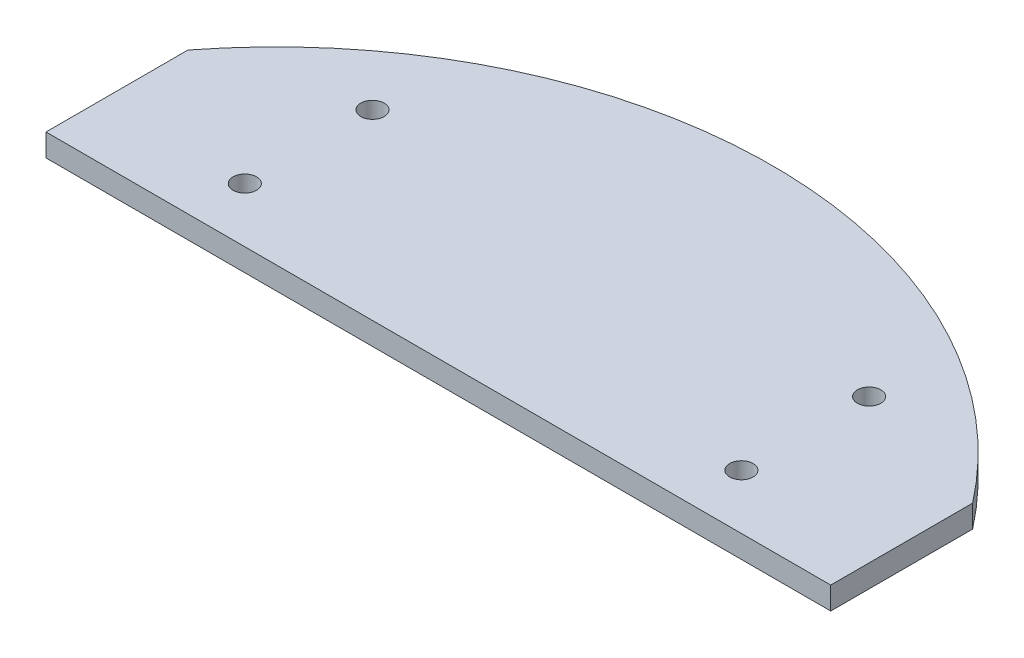
SolidWorks part; units mm, degrees
ref_plane "Front Plane" through (0, 0, 0) normal (0, 0, 1) x (1, 0, 0)
ref_plane "Top Plane" through (0, 0, 0) normal (0, 1, 0) x (1, 0, 0)
ref_plane "Right Plane" through (0, 0, 0) normal (1, 0, 0) x (0, 0, -1)
sketch "Sketch1" plane through (0, 0, 0) normal (0, 1, 0) x (1, 0, 0)
  line L0 (0, 70) -> (0, 22.9088) construction
  line L1 (35, 22.9088) -> (35, 60.6218) construction
  line L3 (0, 0) -> (49.4975, 49.4975) construction
  line L4 (0, 0) -> (26.7878, 64.6716) construction
  line L15 (0, 0) -> (-26.7878, 64.6716) construction
  line L16 (0, 0) -> (-49.4975, 49.4975) construction
  line L18 (-55.3067, 42.9088) -> (-55.3067, 22.9088)
  line L19 (55.3067, 42.9088) -> (55.3067, 22.9088)
  line L20 (-55.3067, 22.9088) -> (55.3067, 22.9088)
  arc A14 (55.3067, 42.9088) -> (-55.3067, 42.9088) centre (0, 0) ccw
  circle A17 centre (35, 48.6218) radius 1.65
  circle A18 centre (35, 30.6218) radius 1.65
  circle A19 centre (-35, 30.6218) radius 1.65
  circle A20 centre (-35, 48.6218) radius 1.65
  dimension "D1" = 3.3
  dimension "D5" = 12
  dimension "D9" = 20
  dimension "D2" = 35
  dimension "D3" = 18
  dimension "D4" = 22.5
extrude "Boss-Extrude2" add sketch "Sketch1" along normal blind 3.175
